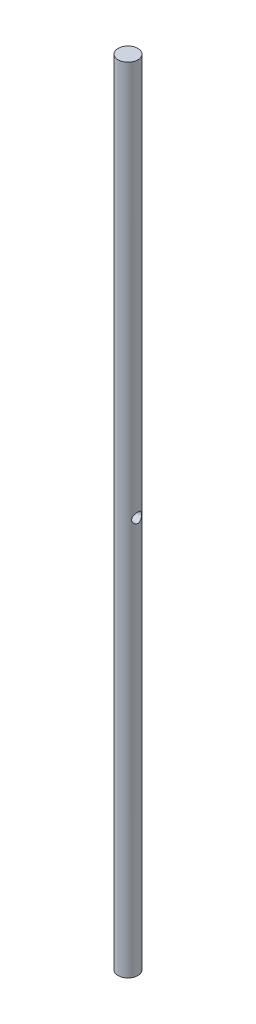
SolidWorks part; units mm, degrees
ref_plane "Front Plane" through (0, 0, 0) normal (0, 0, 1) x (1, 0, 0)
ref_plane "Top Plane" through (0, 0, 0) normal (0, 1, 0) x (1, 0, 0)
ref_plane "Right Plane" through (0, 0, 0) normal (1, 0, 0) x (0, 0, -1)
sketch "Sketch1" plane through (0, 0, 0) normal (0, 1, 0) x (1, 0, 0)
  circle A0 centre (0, 0) radius 1
  dimension "D1" = 2
extrude "Boss-Extrude1" add sketch "Sketch1" along normal blind 80
sketch "Sketch2" plane through (0, 0, 0) normal (1, 0, 0) x (0, 0, -1)
  line L0 (-1, 0) -> (1, 0) construction
  circle A0 centre (0, 40) radius 0.5
  dimension "D1" = 1
  dimension "D2" = 40
extrude "Cut-Extrude1" cut sketch "Sketch2" against normal through all both and the other way through all
